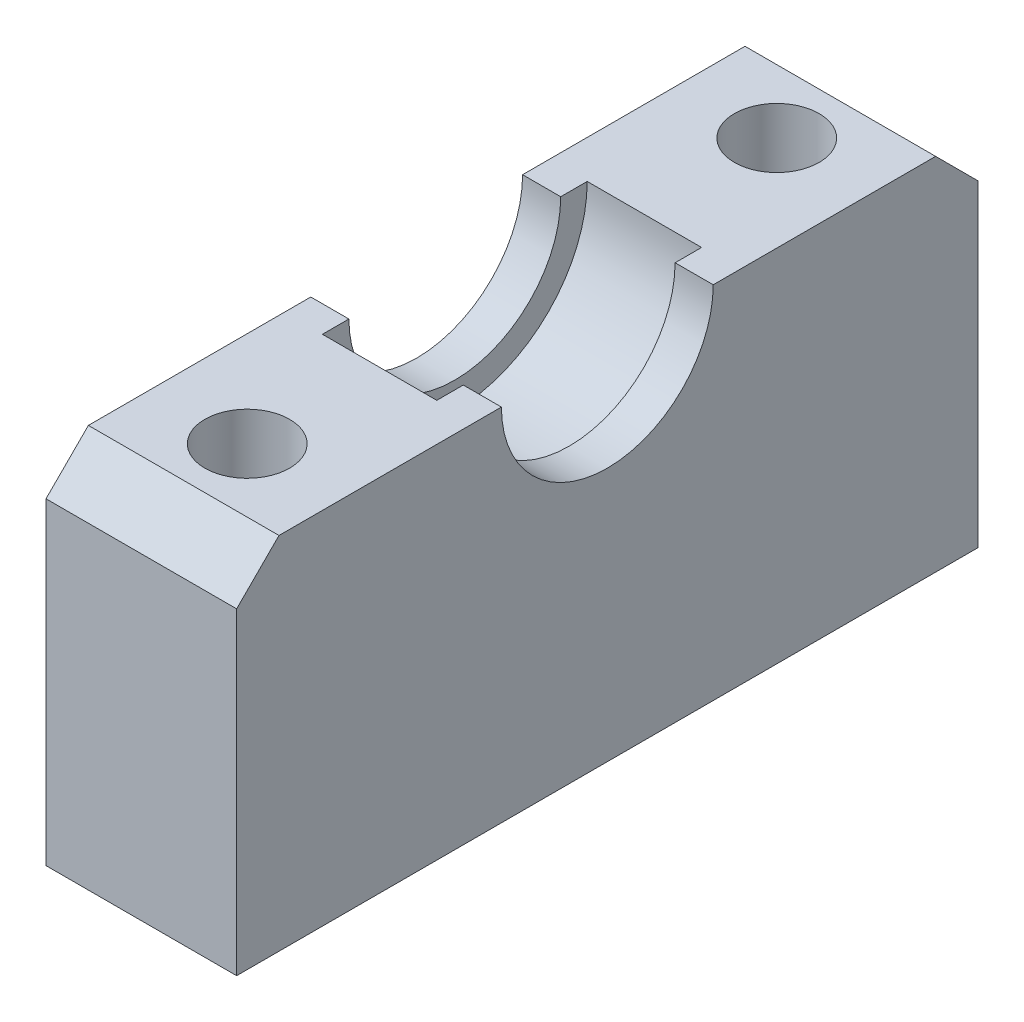
SolidWorks part; units mm, degrees
ref_plane "Front Plane" through (0, 0, 0) normal (0, 0, 1) x (1, 0, 0)
ref_plane "Top Plane" through (0, 0, 0) normal (0, 1, 0) x (1, 0, 0)
ref_plane "Right Plane" through (0, 0, 0) normal (1, 0, 0) x (0, 0, -1)
sketch "Sketch1" plane through (0, 0, 0) normal (1, 0, 0) x (0, 0, -1)
  line L0 (5, 8.5) -> (17.5, 8.5)
  line L1 (-17.5, -8.5) -> (17.5, -8.5)
  line L2 (-17.5, -8.5) -> (-17.5, 8.5)
  line L3 (-17.5, 8.5) -> (-5, 8.5)
  line L4 (17.5, -8.5) -> (17.5, 8.5)
  line L5 (-17.5, -8.5) -> (17.5, 8.5) construction
  line L6 (-17.5, 8.5) -> (17.5, -8.5) construction
  line L7 (0, 0) -> (0, 8.5) construction
  line L8 (0, 8.5) -> (5, 8.5) construction
  arc A0 (-5, 8.5) -> (5, 8.5) centre (0, 8.5) ccw
  point P0 (0, 0)
  dimension "D3" = 10
  dimension "D1" = 17
  dimension "D2" = 35
extrude "Boss-Extrude1" add sketch "Sketch1" along normal blind 4.5 and the other way blind 4.5
sketch "Sketch2" plane through (0, 0, 0) normal (1, 0, 0) x (0, 0, -1)
  circle A0 centre (0, 8.5) radius 6.25
  dimension "D1" = 12.5
extrude "Cut-Extrude1" cut sketch "Sketch2" against normal blind 2.7 and the other way blind 2.7
sketch "Sketch3" plane through (0, 8.5, 0) normal (0, 1, 0) x (1, 0, 0)
  line L0 (-4.5, 17.5) -> (4.5, 17.5) construction
  line L1 (0, 12.5) -> (0, 0) construction
  line L2 (0, 0) -> (0, -12.5) construction
  line L3 (-4.5, -17.5) -> (4.5, -17.5) construction
  circle A0 centre (0, 12.5) radius 2
  circle A1 centre (0, -12.5) radius 2
  dimension "D3" = 4
  dimension "D4" = 4
  dimension "D1" = 5
  dimension "D2" = 5
extrude "Cut-Extrude3" cut sketch "Sketch3" against normal through all
chamfer "Chamfer1" distance 2 angle 45 2 edges at (0, 8.5, -17.5) (0, 8.5, 17.5)
